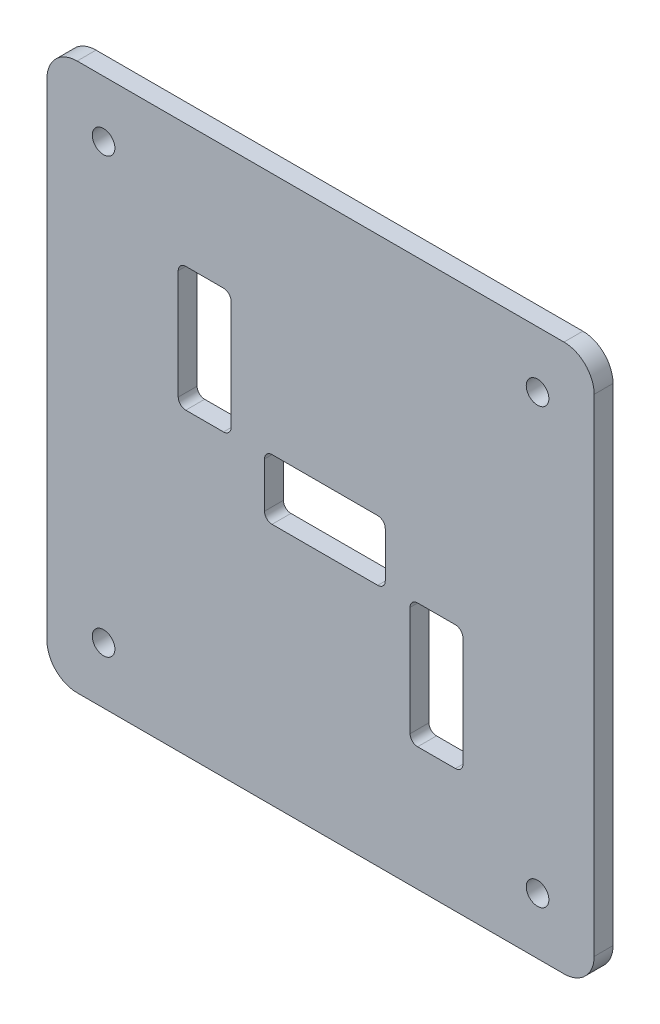
SolidWorks part; units mm, degrees
ref_plane "Front Plane" through (0, 0, 0) normal (0, 0, 1) x (1, 0, 0)
ref_plane "Top Plane" through (0, 0, 0) normal (0, 1, 0) x (1, 0, 0)
ref_plane "Right Plane" through (0, 0, 0) normal (1, 0, 0) x (0, 0, -1)
sketch "Sketch1" plane through (0, 0, 0) normal (1, 0, 0) x (0, 0, -1)
  line L1 (0, 12.5) -> (34.45, 12.5)
  line L2 (0, 1.5) -> (0, -12.5)
  line L3 (0, -12.5) -> (34.45, -12.5)
  line L4 (34.45, 12.5) -> (34.45, -12.5)
  circle A0 centre (0, 0) radius 1.5
  circle A1 centre (0, 0) radius 12.5 construction
  arc A2 (0, 12.5) -> (0, -12.5) centre (0, 0) ccw
  dimension "D1" = 3
  dimension "D2" = 25
  dimension "D3" = 34.45
extrude "Boss-Extrude1" add sketch "Sketch1" along normal blind 2.5 contours L1 A2 A0 L3 L4 region at (0, 0, -12.3069)
sketch "Sketch2" plane through (0, 0, 0) normal (-1, 0, 0) x (0, 0, 1)
  circle A0 centre (0, 0) radius 1.5
  circle A1 centre (0, 0) radius 4.5
  dimension "D1" = 9
  dimension "D2" = 3
extrude "Boss-Extrude2" add sketch "Sketch2" along normal blind 1.8 and the other way offset from surface 0.75 other way up to face at (2.5, 0, -14.1)
sketch "Sketch4" plane through (2.5, 0, 0) normal (1, 0, 0) x (0, 0, -1)
  circle A0 centre (0, 0) radius 2.5
extrude "Cut-Extrude1" cut sketch "Sketch4" against normal blind 2
sketch "Sketch5" plane through (2.5, 0, 0) normal (1, 0, 0) x (0, 0, -1)
  circle A0 centre (0, 0) radius 4.5
  circle A1 centre (0, 0) radius 2.5
  dimension "D1" = 9
  dimension "D2" = 5
extrude "Boss-Extrude3" add sketch "Sketch5" along normal blind 0.75
sketch "Sketch6" plane through (0, 0, -34.45) normal (0, 0, -1) x (-1, 0, 0)
  line L1 (-8.8125, 36.25) -> (53.3216, 36.25)
  line L3 (6.25, -36.25) -> (53.3216, -36.25)
  line L4 (53.3216, 36.25) -> (53.3216, -36.25)
  line L6 (53.3216, -36.25) -> (-19.1784, 36.25) construction
  line L7 (6.25, -36.25) -> (-19.1784, -36.25)
  line L9 (-8.8125, 36.25) -> (-19.1784, 36.25)
  line L10 (-19.1784, -36.25) -> (-19.1784, 36.25)
  line L11 (53.3216, 36.25) -> (-19.1784, -36.25) construction
  point P4 (17.0716, 0)
  dimension "D1" = 72.5
  dimension "D2" = 72.5
extrude "Boss-Extrude4" add sketch "Sketch6" against normal blind 2.5
ref_plane "Plane1" through (-17.0716, 0, 0) normal (1, 0, 0) x (0, 0, -1)
ref_plane "Plane2" through (9.4784, 0, 0) normal (1, 0, 0) x (0, 0, -1)
sketch "Sketch7" plane through (0, 0, -31.95) normal (0, 0, 1) x (1, 0, 0)
  line L6 (19.1784, 36.25) -> (19.1784, -36.25) construction
  line L7 (1.7881, -3.3824) -> (-5.2119, -3.3824)
  line L12 (1.7881, -3.3824) -> (1.7881, -19.8824)
  line L18 (1.7881, -19.8824) -> (-5.2119, -19.8824)
  line L19 (-5.2119, -3.3824) -> (-5.2119, -19.8824)
  line L20 (1.7881, -3.3824) -> (-5.2119, -19.8824) construction
  line L21 (1.7881, -19.8824) -> (-5.2119, -3.3824) construction
  line L22 (-24.5, -4) -> (-8.5, -4)
  line L23 (-24.5, -4) -> (-24.5, 4)
  line L24 (-24.5, 4) -> (-8.5, 4)
  line L25 (-8.5, -4) -> (-8.5, 4)
  line L26 (-24.5, -4) -> (-8.5, 4) construction
  line L27 (-24.5, 4) -> (-8.5, -4) construction
  line L28 (19.1784, -36.25) -> (-53.3216, -36.25) construction
  line L29 (25.8225, 0) -> (-25.8225, 0) construction
  line L30 (-17.0716, -1.375) -> (-17.0716, 1.375) construction
  circle A0 centre (11.6784, -28.75) radius 1.5
  circle A1 centre (11.6784, 28.75) radius 1.5
  circle A2 centre (-45.8216, 28.75) radius 1.5
  circle A3 centre (-45.8216, -28.75) radius 1.5
  point P0 (-16.5, 0)
  point P2 (-1.7119, -11.6324)
  dimension "D1" = 16
  dimension "D5" = 3
  dimension "D2" = 16.5
  dimension "D3" = 7
  dimension "D4" = 8
  dimension "D6" = 7.5
  dimension "D7" = 7.5
extrude "Cut-Extrude2" cut sketch "Sketch7" against normal up to next
sketch "Sketch8" plane through (0, 0, 0) normal (0, 1, 0) x (1, 0, 0)
  line L1 (13.2433, 31.95) -> (10.7433, 31.95)
  line L2 (13.2433, 31.95) -> (13.2433, 24.6995)
  line L4 (10.7433, 31.95) -> (10.7433, 24.0093)
  line L5 (0, 0) -> (0, 31.95) construction
  line L10 (2.5, 0) -> (2.5, 31.95) construction
  line L12 (0, 11.3659) -> (0, 9.0717)
  line L13 (0, 9.0717) -> (2.5, 9.0717)
  line L14 (2.5, 11.6667) -> (2.5, 9.0717)
  line L15 (19.1784, 31.95) -> (-53.3216, 31.95) construction
  arc A0 (10.7433, 24.0093) -> (6.5504, 19.0748) centre (5.7433, 24.0093) cw
  arc A1 (6.5459, 16.5749) -> (2.5, 11.6667) centre (7.5, 11.6667) ccw
  arc A3 (6.5459, 16.5749) -> (13.2433, 24.6995) centre (4.9666, 24.6995) ccw
  arc A4 (6.5504, 19.0748) -> (0, 11.3659) centre (7.8114, 11.3659) ccw
  point P21 (0, 24.8672)
  dimension "D3" = 5
  dimension "D1" = 2.5
  dimension "D2" = 2.5
sketch "Sketch9" plane through (0, -12.5, 0) normal (0, -1, 0) x (1, 0, 0)
  line L0 (2.5, 0) -> (2.5, -31.95) construction
  line L1 (0, -31.95) -> (2.5, -31.95)
  line L2 (0, -31.95) -> (0, -9.5612)
  line L3 (0, -9.5612) -> (2.5, -9.5612)
  line L4 (2.5, -31.95) -> (2.5, -9.5612)
extrude "Cut-Extrude3" cut sketch "Sketch9" against normal up to next
extrude "Boss-Extrude5" add sketch "Sketch8" along normal mid plane 25
fillet "Fillet1" radius 4 4 edges at (10.7433, 0, -31.95) (13.2433, 0, -31.95) (11.9933, 12.5, -31.95) (11.9933, -12.5, -31.95)
fillet "Fillet2" radius 1 8 edges at (-5.2119, -3.3824, -33.2) (-5.2119, -19.8824, -33.2) (1.7881, -3.3824, -33.2) (-8.5, 4, -33.2) (1.7881, -19.8824, -33.2) (-8.5, -4, -33.2) (-24.5, 4, -33.2) (-24.5, -4, -33.2)
fillet "Fillet3" radius 4 4 edges at (19.1784, -36.25, -33.2) (19.1784, 36.25, -33.2) (-53.3216, 36.25, -33.2) (-53.3216, -36.25, -33.2)
sketch "Sketch10" plane through (0, 0, 0) normal (0, 1, 0) x (1, 0, 0)
  line L0 (15.1784, 31.95) -> (19.1784, 31.95) construction
  line L1 (18.0242, 31.95) -> (-8.6002, 31.95)
  line L2 (18.0242, 31.95) -> (18.0242, -16.5748)
  line L3 (18.0242, -16.5748) -> (-8.6002, -16.5748)
  line L4 (-8.6002, 31.95) -> (-8.6002, -16.5748)
extrude "Cut-Extrude4" cut sketch "Sketch10" against normal through all both and the other way through all
ref_axis "Axis1" through (-17.0716, 0, -34.575) along (0, 0, 1)
pattern_circular "CirPattern1" count 2 over 360 about axis through (-17.0716, 0, -34.575) along (0, 0, 1) of face at (-5.2119, -11.6324, -33.2) of face at (-4.8154, -3.7789, -33.2) of face at (-1.7119, -3.3824, -33.2) of face at (1.3917, -3.7789, -33.2) of face at (1.7881, -11.6324, -33.2) of face at (1.3917, -19.486, -33.2) of face at (-1.7119, -19.8824, -33.2) of face at (-4.8154, -19.486, -33.2)
